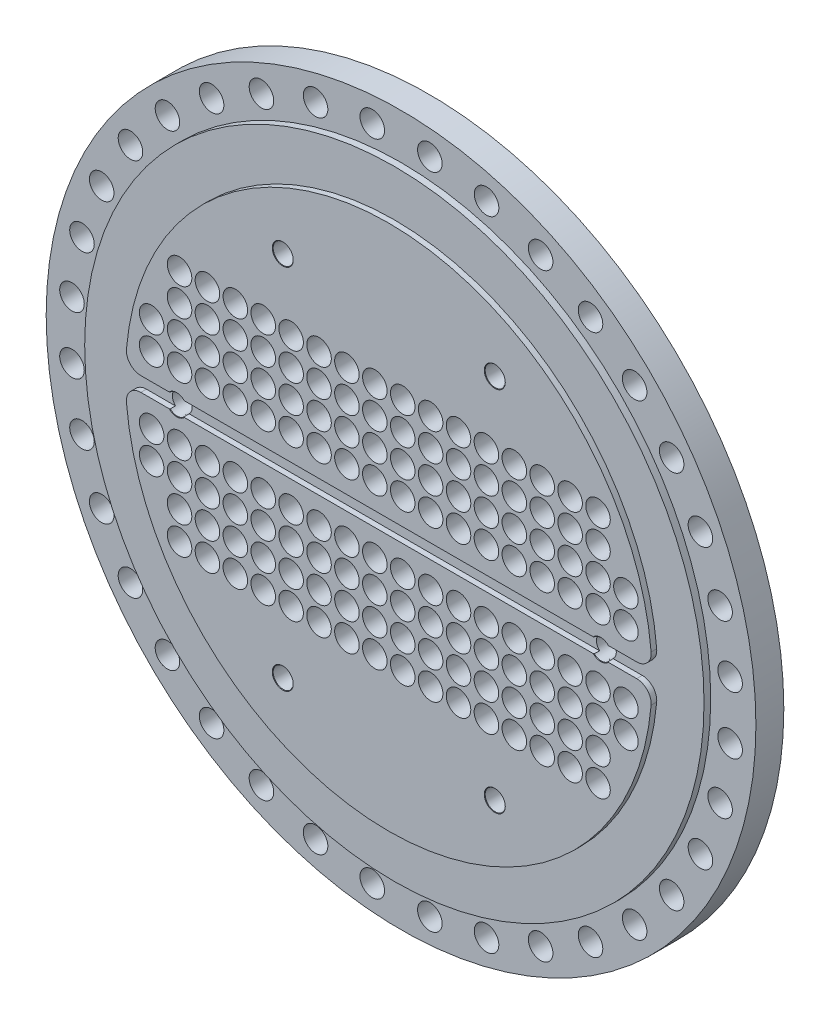
SolidWorks part; units mm, degrees
material "AISI 304"
ref_plane "Front Plane" through (0, 0, 0) normal (0, 0, 1) x (1, 0, 0)
ref_plane "Top Plane" through (0, 0, 0) normal (0, 1, 0) x (1, 0, 0)
ref_plane "Right Plane" through (0, 0, 0) normal (1, 0, 0) x (0, 0, -1)
sketch "Sketch1" plane through (0, 0, 0) normal (0, 0, 1) x (1, 0, 0)
  line L0 (0, 0) -> (0, 318) construction
  line L1 (0, 0) -> (236, 0) construction
  line L3 (222.1458, -6.5) -> (-222.1458, -6.5)
  line L5 (222.1458, 6.5) -> (-222.1458, 6.5)
  circle A0 centre (0, 0) radius 277.5
  circle A1 centre (0, 0) radius 318
  arc A2 (-235.096, -20.6368) -> (235.096, -20.6368) centre (0, 0) ccw
  arc A3 (235.096, 20.6368) -> (-235.096, 20.6368) centre (0, 0) ccw
  arc A4 (235.096, -20.6368) -> (222.1458, -6.5) centre (222.1458, -19.5) ccw
  arc A5 (235.096, 20.6368) -> (222.1458, 6.5) centre (222.1458, 19.5) cw
  arc A6 (-235.096, -20.6368) -> (-222.1458, -6.5) centre (-222.1458, -19.5) cw
  arc A7 (-235.096, 20.6368) -> (-222.1458, 6.5) centre (-222.1458, 19.5) ccw
  dimension "D1" = 636
  dimension "D2" = 555
  dimension "D3" = 472
  dimension "D5" = 13
  dimension "D4" = 13
extrude "Boss-Extrude1" add sketch "Sketch1" along normal mid plane 25 contours A1
extrude "Boss-Extrude2" add sketch "Sketch1<3>" along normal mid plane 37 contours A0
sketch "Sketch1<3>" plane through (0, 0, 0) normal (0, 0, 1) x (1, 0, 0) same geometry as "Sketch1"
extrude "Boss-Extrude3" add sketch "Sketch1<4>" along normal mid plane 47 contours A6 A2 A4 L3 | A3 A7 L5 A5 region at (0, -103.7775, 0)
sketch "Sketch1<4>" plane through (0, 0, 0) normal (0, 0, 1) x (1, 0, 0) same geometry as "Sketch1"
sketch "Sketch2" plane through (0, 0, 12.5) normal (0, 0, 1) x (1, 0, 0)
  line L0 (0, 0) -> (0, 296) construction
  line L1 (0, 0) -> (25.7981, 294.8736) construction
  circle A0 centre (0, 0) radius 296 construction
  circle A1 centre (25.7981, 294.8736) radius 11
  circle A2 centre (76.6104, 285.914) radius 11
  circle A3 centre (125.095, 268.2671) radius 11
  circle A4 centre (169.7786, 242.469) radius 11
  circle A5 centre (209.3036, 209.3036) radius 11
  circle A6 centre (242.469, 169.7786) radius 11
  circle A7 centre (268.2671, 125.095) radius 11
  circle A8 centre (285.914, 76.6104) radius 11
  circle A9 centre (294.8736, 25.7981) radius 11
  circle A10 centre (294.8736, -25.7981) radius 11
  circle A11 centre (285.914, -76.6104) radius 11
  circle A12 centre (268.2671, -125.095) radius 11
  circle A13 centre (242.469, -169.7786) radius 11
  circle A14 centre (209.3036, -209.3036) radius 11
  circle A15 centre (169.7786, -242.469) radius 11
  circle A16 centre (125.095, -268.2671) radius 11
  circle A17 centre (76.6104, -285.914) radius 11
  circle A18 centre (25.7981, -294.8736) radius 11
  circle A19 centre (-25.7981, -294.8736) radius 11
  circle A20 centre (-76.6104, -285.914) radius 11
  circle A21 centre (-125.095, -268.2671) radius 11
  circle A22 centre (-169.7786, -242.469) radius 11
  circle A23 centre (-209.3036, -209.3036) radius 11
  circle A24 centre (-242.469, -169.7786) radius 11
  circle A25 centre (-268.2671, -125.095) radius 11
  circle A26 centre (-285.914, -76.6104) radius 11
  circle A27 centre (-294.8736, -25.7981) radius 11
  circle A28 centre (-294.8736, 25.7981) radius 11
  circle A29 centre (-285.914, 76.6104) radius 11
  circle A30 centre (-268.2671, 125.095) radius 11
  circle A31 centre (-242.469, 169.7786) radius 11
  circle A32 centre (-209.3036, 209.3036) radius 11
  circle A33 centre (-169.7786, 242.469) radius 11
  circle A34 centre (-125.095, 268.2671) radius 11
  circle A35 centre (-76.6104, 285.914) radius 11
  circle A36 centre (-25.7981, 294.8736) radius 11
  dimension "D1" = 592
  dimension "D3" = 22
  dimension "D2" = 5
  dimension "D4" = 36
extrude "Cut-Extrude1" cut sketch "Sketch2" against normal up to next (25 mm away)
sketch "Sketch3" plane through (0, 0, 23.5) normal (0, 0, 1) x (1, 0, 0)
  line L0 (0, 0) -> (0, 318) construction
  line L1 (0, 0) -> (236.4322, 0) construction
  circle A0 centre (12.5, 30) radius 11
  circle A1 centre (0, 0) radius 318 construction
  circle A2 centre (37.5, 30) radius 11
  circle A3 centre (62.5, 30) radius 11
  circle A4 centre (87.5, 30) radius 11
  circle A5 centre (112.5, 30) radius 11
  circle A6 centre (137.5, 30) radius 11
  circle A7 centre (162.5, 30) radius 11
  circle A8 centre (187.5, 30) radius 11
  circle A9 centre (212.5, 30) radius 11
  circle A10 centre (37.5, 55) radius 11
  circle A11 centre (62.5, 55) radius 11
  circle A12 centre (87.5, 55) radius 11
  circle A13 centre (112.5, 55) radius 11
  circle A14 centre (137.5, 55) radius 11
  circle A15 centre (162.5, 55) radius 11
  circle A16 centre (187.5, 55) radius 11
  circle A17 centre (212.5, 55) radius 11
  circle A18 centre (37.5, 80) radius 11
  circle A19 centre (62.5, 80) radius 11
  circle A20 centre (87.5, 80) radius 11
  circle A21 centre (112.5, 80) radius 11
  circle A22 centre (137.5, 80) radius 11
  circle A23 centre (162.5, 80) radius 11
  circle A24 centre (187.5, 80) radius 11
  circle A26 centre (37.5, 105) radius 11
  circle A27 centre (62.5, 105) radius 11
  circle A28 centre (87.5, 105) radius 11
  circle A29 centre (112.5, 105) radius 11
  circle A30 centre (137.5, 105) radius 11
  circle A31 centre (162.5, 105) radius 11
  circle A32 centre (187.5, 105) radius 11
  circle A34 centre (12.5, 55) radius 11
  circle A35 centre (12.5, 80) radius 11
  circle A36 centre (12.5, 105) radius 11
  circle A37 centre (212.5, 80) radius 11 [skipped]
  circle A38 centre (212.5, 105) radius 11 [skipped]
  circle A39 centre (-12.5, 105) radius 11
  circle A40 centre (-12.5, 80) radius 11
  circle A41 centre (-12.5, 55) radius 11
  circle A42 centre (-187.5, 105) radius 11
  circle A43 centre (-162.5, 105) radius 11
  circle A44 centre (-137.5, 105) radius 11
  circle A45 centre (-112.5, 105) radius 11
  circle A46 centre (-87.5, 105) radius 11
  circle A47 centre (-62.5, 105) radius 11
  circle A48 centre (-37.5, 105) radius 11
  circle A49 centre (-187.5, 80) radius 11
  circle A50 centre (-162.5, 80) radius 11
  circle A51 centre (-137.5, 80) radius 11
  circle A52 centre (-112.5, 80) radius 11
  circle A53 centre (-87.5, 80) radius 11
  circle A54 centre (-62.5, 80) radius 11
  circle A55 centre (-37.5, 80) radius 11
  circle A56 centre (-212.5, 55) radius 11
  circle A57 centre (-187.5, 55) radius 11
  circle A58 centre (-162.5, 55) radius 11
  circle A59 centre (-137.5, 55) radius 11
  circle A60 centre (-112.5, 55) radius 11
  circle A61 centre (-87.5, 55) radius 11
  circle A62 centre (-62.5, 55) radius 11
  circle A63 centre (-37.5, 55) radius 11
  circle A64 centre (-212.5, 30) radius 11
  circle A65 centre (-187.5, 30) radius 11
  circle A66 centre (-162.5, 30) radius 11
  circle A67 centre (-137.5, 30) radius 11
  circle A68 centre (-112.5, 30) radius 11
  circle A69 centre (-87.5, 30) radius 11
  circle A70 centre (-62.5, 30) radius 11
  circle A71 centre (-37.5, 30) radius 11
  circle A72 centre (-12.5, 30) radius 11
  circle A73 centre (-212.5, -30) radius 11
  circle A74 centre (-212.5, -55) radius 11
  circle A75 centre (-12.5, -30) radius 11
  circle A76 centre (-37.5, -30) radius 11
  circle A77 centre (-62.5, -30) radius 11
  circle A78 centre (-87.5, -30) radius 11
  circle A79 centre (-112.5, -30) radius 11
  circle A80 centre (-137.5, -30) radius 11
  circle A81 centre (-162.5, -30) radius 11
  circle A82 centre (-187.5, -30) radius 11
  circle A83 centre (-37.5, -55) radius 11
  circle A84 centre (-62.5, -55) radius 11
  circle A85 centre (-87.5, -55) radius 11
  circle A86 centre (-112.5, -55) radius 11
  circle A87 centre (-137.5, -55) radius 11
  circle A88 centre (-162.5, -55) radius 11
  circle A89 centre (-187.5, -55) radius 11
  circle A90 centre (-37.5, -80) radius 11
  circle A91 centre (-62.5, -80) radius 11
  circle A92 centre (-87.5, -80) radius 11
  circle A93 centre (-112.5, -80) radius 11
  circle A94 centre (-137.5, -80) radius 11
  circle A95 centre (-162.5, -80) radius 11
  circle A96 centre (-187.5, -80) radius 11
  circle A97 centre (-37.5, -105) radius 11
  circle A98 centre (-62.5, -105) radius 11
  circle A99 centre (-87.5, -105) radius 11
  circle A100 centre (-112.5, -105) radius 11
  circle A101 centre (-137.5, -105) radius 11
  circle A102 centre (-162.5, -105) radius 11
  circle A103 centre (-187.5, -105) radius 11
  circle A104 centre (-12.5, -55) radius 11
  circle A105 centre (-12.5, -80) radius 11
  circle A106 centre (-12.5, -105) radius 11
  circle A107 centre (12.5, -105) radius 11
  circle A108 centre (12.5, -80) radius 11
  circle A109 centre (12.5, -55) radius 11
  circle A110 centre (187.5, -105) radius 11
  circle A111 centre (162.5, -105) radius 11
  circle A112 centre (137.5, -105) radius 11
  circle A113 centre (112.5, -105) radius 11
  circle A114 centre (87.5, -105) radius 11
  circle A115 centre (62.5, -105) radius 11
  circle A116 centre (37.5, -105) radius 11
  circle A117 centre (187.5, -80) radius 11
  circle A118 centre (162.5, -80) radius 11
  circle A119 centre (137.5, -80) radius 11
  circle A120 centre (112.5, -80) radius 11
  circle A121 centre (87.5, -80) radius 11
  circle A122 centre (62.5, -80) radius 11
  circle A123 centre (37.5, -80) radius 11
  circle A124 centre (212.5, -55) radius 11
  circle A125 centre (187.5, -55) radius 11
  circle A126 centre (162.5, -55) radius 11
  circle A127 centre (137.5, -55) radius 11
  circle A128 centre (112.5, -55) radius 11
  circle A129 centre (87.5, -55) radius 11
  circle A130 centre (62.5, -55) radius 11
  circle A131 centre (37.5, -55) radius 11
  circle A132 centre (212.5, -30) radius 11
  circle A133 centre (187.5, -30) radius 11
  circle A134 centre (162.5, -30) radius 11
  circle A135 centre (137.5, -30) radius 11
  circle A136 centre (112.5, -30) radius 11
  circle A137 centre (87.5, -30) radius 11
  circle A138 centre (62.5, -30) radius 11
  circle A139 centre (37.5, -30) radius 11
  circle A140 centre (12.5, -30) radius 11
  dimension "D1" = 22
  dimension "D2" = 30
  dimension "D3" = 12.5
  dimension "D4" = 9
  dimension "D5" = 4
extrude "Cut-Extrude2" cut sketch "Sketch3" against normal up to next (47 mm away)
sketch "Sketch4" plane through (0, 0, 23.5) normal (0, 0, 1) x (1, 0, 0)
  line L0 (0, 0) -> (0, -190) construction
  line L1 (0, 0) -> (95, -164.5448) construction
  line L2 (0, 0) -> (-95, -164.5448) construction
  line L3 (0, 0) -> (-190, 0) construction
  line L4 (0, 0) -> (-95, 164.5448) construction
  line L5 (0, 0) -> (95, 164.5448) construction
  line L6 (0, 0) -> (190, 0) construction
  circle A0 centre (0, 0) radius 190
  point P6 (95, -164.5448)
  dimension "D1" = 380
  dimension "D2" = 30
  dimension "D3" = 6
hole_wizard "3/8 NPT Tapped Hole1" positions "3DSketch2" profile "Sketch6" size "3/8" standard "ANSI Inch"
sketch3d "3DSketch2"
  point P0 (-95, -164.5448, 23.5)
  point P4 (95, -164.5448, 23.5)
  point P7 (190, 0, 23.5)
  point P10 (-190, 0, 23.5)
  point P13 (-95, 164.5448, 23.5)
  point P16 (95, 164.5448, 23.5)
sketch "Sketch6" plane through (-95, -164.5448, 23.5) normal (1, 0, 0) x (0, -1, 0)
  line L0 (0, 0) -> (0, 36.2886)
  line L1 (7.1374, 32) -> (0, 36.2886)
  line L2 (-7.1374, 32) -> (0, 36.2886) construction
  line L3 (7.1374, 32) -> (7.1374, 25)
  line L4 (7.1374, 25) -> (8.2748, 25)
  line L5 (8.2748, 25) -> (9.0117, 0.3863)
  line L6 (9.0117, 0.3863) -> (9.398, 0)
  line L7 (9.398, 0) -> (0, 0)
  line L8 (0, -6.35) -> (0, 107.95) construction
  line L9 (-9.0117, 0.3863) -> (-9.398, 0) construction
  line L11 (-7.1374, 25) -> (-8.2748, 25) construction
  line L12 (-8.2748, 25) -> (-9.0117, 0.3863) construction
  dimension "Tap Drill Dia." = 14.2748
  dimension "Tap Drill Depth" = 32
  dimension "Thread Dia." = 18.0235
  dimension "Thread Angle" = 3.43
  dimension "Thread Depth" = 25
  dimension "C'Sink Dia." = 18.796
  dimension "C'Sink Angle" = 90
  dimension "Drill Angle" = 118
